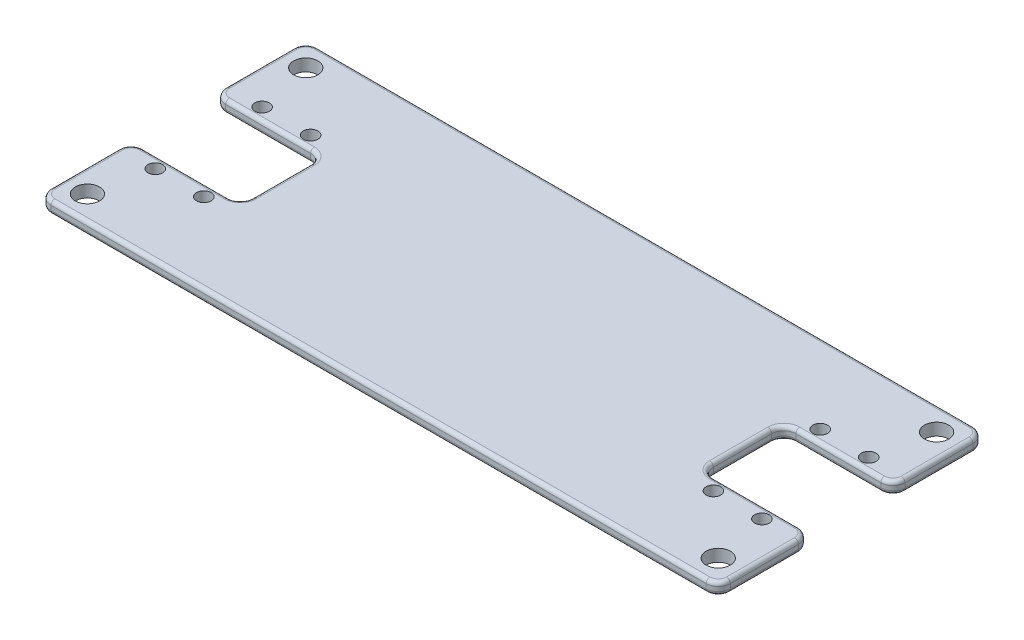
SolidWorks part; units mm, degrees
ref_plane "Front Plane" through (0, 0, 0) normal (0, 0, 1) x (1, 0, 0)
ref_plane "Top Plane" through (0, 0, 0) normal (0, 1, 0) x (1, 0, 0)
ref_plane "Right Plane" through (0, 0, 0) normal (1, 0, 0) x (0, 0, -1)
sketch "Sketch1" plane through (0, 0, 0) normal (0, 1, 0) x (1, 0, 0)
  line L1 (-88.9, -34.925) -> (88.9, -34.925)
  line L2 (-88.9, -34.925) -> (-88.9, 34.925)
  line L3 (-88.9, 34.925) -> (88.9, 34.925)
  line L4 (88.9, -34.925) -> (88.9, 34.925)
  line L5 (-88.9, -34.925) -> (88.9, 34.925) construction
  line L6 (-88.9, 34.925) -> (88.9, -34.925) construction
  point P0 (0, 0)
  dimension "D1" = 69.85
  dimension "D2" = 177.8
extrude "Boss-Extrude1" add sketch "Sketch1" along normal blind 3.175
sketch "Sketch2" plane through (0, 3.175, 0) normal (0, 1, 0) x (1, 0, 0)
  line L0 (-88.9, 34.925) -> (-88.9, -34.925) construction
  line L1 (-82.55, -28.575) -> (82.55, -28.575) construction
  line L2 (-82.55, -28.575) -> (-82.55, 28.575) construction
  line L3 (-82.55, 28.575) -> (82.55, 28.575) construction
  line L4 (82.55, -28.575) -> (82.55, 28.575) construction
  line L5 (-82.55, -28.575) -> (82.55, 28.575) construction
  line L6 (-82.55, 28.575) -> (82.55, -28.575) construction
  line L7 (88.9, 34.925) -> (-88.9, 34.925) construction
  line L9 (88.9, -34.925) -> (88.9, 34.925) construction
  line L10 (-60.325, -10.795) -> (-88.9, -10.795)
  line L11 (-60.325, -10.795) -> (-60.325, 10.795)
  line L12 (-60.325, 10.795) -> (-88.9, 10.795)
  line L13 (60.325, -10.795) -> (88.9, -10.795)
  line L14 (60.325, -10.795) -> (60.325, 10.795)
  line L15 (60.325, 10.795) -> (88.9, 10.795)
  line L16 (88.9, -10.795) -> (88.9, 10.795)
  line L17 (-88.9, 0) -> (96.9512, 0) construction
  line L18 (-88.9, -10.795) -> (-88.9, 10.795)
  line L19 (-60.325, -10.795) -> (-88.9, 10.795) construction
  line L20 (-60.325, 10.795) -> (-88.9, -10.795) construction
  line L21 (60.325, -10.795) -> (88.9, 10.795) construction
  line L22 (60.325, 10.795) -> (88.9, -10.795) construction
  line L23 (-88.9, 13.97) -> (88.9, 13.97) construction
  line L24 (-88.9, -13.97) -> (88.9, -13.97) construction
  circle A0 centre (-82.55, 28.575) radius 3.175
  circle A1 centre (-82.55, -28.575) radius 3.175
  circle A2 centre (82.55, 28.575) radius 3.175
  circle A3 centre (82.55, -28.575) radius 3.175
  circle A4 centre (-66.675, 13.97) radius 1.905
  circle A5 centre (-79.375, 13.97) radius 1.905
  circle A6 centre (-66.675, -13.97) radius 1.905
  circle A7 centre (-79.375, -13.97) radius 1.905
  circle A8 centre (66.675, 13.97) radius 1.905
  circle A9 centre (79.375, 13.97) radius 1.905
  circle A10 centre (66.675, -13.97) radius 1.905
  circle A11 centre (79.375, -13.97) radius 1.905
  point P0 (0, 0)
  point P14 (-74.6125, 0)
  point P18 (74.6125, 0)
  dimension "D1" = 6.35
  dimension "D2" = 6.35
  dimension "D3" = 6.35
  dimension "D4" = 6.35
  dimension "D12" = 3.81
  dimension "D5" = 6.35
  dimension "D6" = 6.35
  dimension "D7" = 28.575
  dimension "D8" = 21.59
  dimension "D9" = 3.175
  dimension "D10" = 3.175
  dimension "D11" = 12.7
  dimension "D13" = 9.525
  dimension "D14" = 12.7
  dimension "D15" = 9.525
extrude "Cut-Extrude1" cut sketch "Sketch2" against normal through all
fillet "Fillet1" radius 3.175 12 edges at (88.9, 1.5875, -34.925) (88.9, 1.5875, 34.925) (-88.9, 1.5875, -34.925) (-88.9, 1.5875, 34.925) (88.9, 1.5875, 10.795) (60.325, 1.5875, 10.795) (60.325, 1.5875, -10.795) (88.9, 1.5875, -10.795) (-88.9, 1.5875, 10.795) (-60.325, 1.5875, 10.795) (-60.325, 1.5875, -10.795) (-88.9, 1.5875, -10.795)
fillet "Fillet2" radius 1 48 edges at (-87.9701, 0, 33.9951) (-88.9, 0, 22.86) (-87.9701, 0, 11.7249) (-74.6125, 0, 10.795) (-61.2549, 0, 9.8651) (-60.325, 0, 0) (-61.2549, 0, -9.8651) (-74.6125, 0, -10.795) (-87.9701, 0, -11.7249) (-88.9, 0, -22.86) (-87.9701, 0, -33.9951) (0, 0, -34.925) (87.9701, 0, -33.9951) (88.9, 0, -22.86) (87.9701, 0, -11.7249) (74.6125, 0, -10.795) (61.2549, 0, -9.8651) (60.325, 0, 0) (61.2549, 0, 9.8651) (74.6125, 0, 10.795) (87.9701, 0, 11.7249) (88.9, 0, 22.86) (87.9701, 0, 33.9951) (-87.9701, 3.175, 33.9951) (-88.9, 3.175, 22.86) (-87.9701, 3.175, 11.7249) (-74.6125, 3.175, 10.795) (-61.2549, 3.175, 9.8651) (-60.325, 3.175, 0) (-61.2549, 3.175, -9.8651) (-74.6125, 3.175, -10.795) (-87.9701, 3.175, -11.7249) (-88.9, 3.175, -22.86) (-87.9701, 3.175, -33.9951) (0, 3.175, -34.925) (87.9701, 3.175, -33.9951) (88.9, 3.175, -22.86) (87.9701, 3.175, -11.7249) (74.6125, 3.175, -10.795) (61.2549, 3.175, -9.8651) (60.325, 3.175, 0) (61.2549, 3.175, 9.8651) (74.6125, 3.175, 10.795) (87.9701, 3.175, 11.7249) (88.9, 3.175, 22.86) (87.9701, 3.175, 33.9951) (0, 0, 34.925) (0, 3.175, 34.925)
